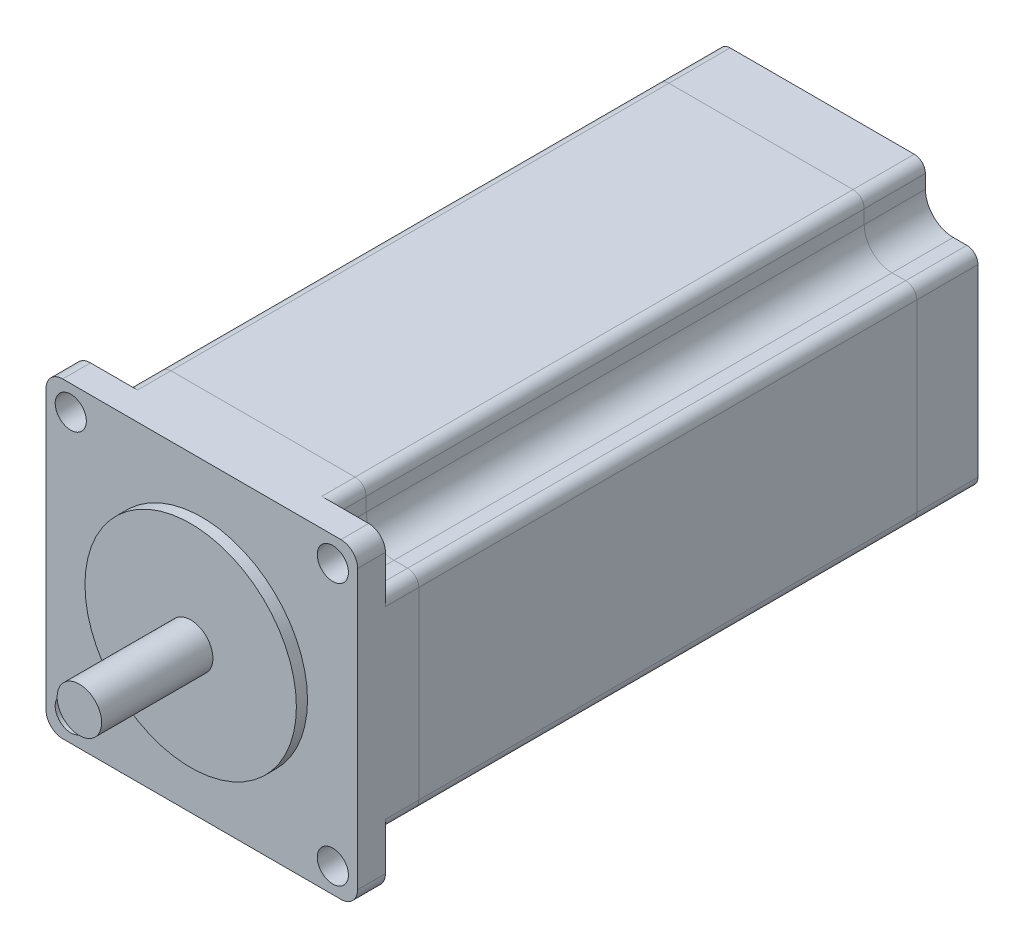
SolidWorks part; units mm, degrees
ref_plane "Front Plane" through (0, 0, 0) normal (0, 0, 1) x (1, 0, 0)
ref_plane "Top Plane" through (0, 0, 0) normal (0, 1, 0) x (1, 0, 0)
ref_plane "Right Plane" through (0, 0, 0) normal (1, 0, 0) x (0, 0, -1)
ref_plane "Plane1" through (0, 0, 0) normal (0, 0, -1) x (-1, 0, 0)
ref_axis "Axis Motor" through (0, 0, -24.3683) along (0, 0, 1)
sketch "Sketch1" plane through (0, 0, 0) normal (0, 0, -1) x (-1, 0, 0)
  line L0 (-23, 28) -> (-28, 23)
  line L1 (-28, 23) -> (-28, -23)
  line L2 (-28, -23) -> (-23, -28)
  line L3 (-23, -28) -> (23, -28)
  line L4 (23, -28) -> (28, -23)
  line L5 (28, -23) -> (28, 23)
  line L6 (28, 23) -> (23, 28)
  line L7 (23, 28) -> (-23, 28)
  line L8 (0, 0) -> (28, 0) construction
  line L9 (0, 0) -> (0, -13.2452) construction
  point P8 (0, -28)
  point P10 (28, 0)
  dimension "D1" = 56
  dimension "D2" = 56
  dimension "D3" = 135
  dimension "D4" = 5
extrude "Boss-Extrude1" add sketch "Sketch1" against normal blind 11.5
sketch "Sketch2" plane through (0, 0, 11.5) normal (0, 0, 1) x (1, 0, 0)
  line L12 (23, 28) -> (-23, 28)
  line L13 (-23, 28) -> (-28, 23)
  line L14 (-28, 23) -> (-28, -23)
  line L15 (-28, -23) -> (-23, -28)
  line L16 (-23, -28) -> (23, -28)
  line L17 (23, -28) -> (28, -23)
  line L18 (28, -23) -> (28, 23)
  line L19 (28, 23) -> (23, 28)
  line L20 (23, 28) -> (-23, 28)
  line L21 (-23, 28) -> (-28, 23)
  line L22 (-28, 23) -> (-28, -23)
  line L23 (-28, -23) -> (-23, -28)
  line L24 (-23, -28) -> (23, -28)
  line L25 (23, -28) -> (28, -23)
  line L26 (28, -23) -> (28, 23)
  line L27 (28, 23) -> (23, 28)
  dimension "D1" = 0
extrude "Boss-Extrude2" add sketch "Sketch2" along normal blind 90
sketch "Sketch3" plane through (0, 0, 101.5) normal (0, 0, 1) x (1, 0, 0)
  line L15 (28, 23) -> (23, 28)
  line L16 (23, 28) -> (-23, 28)
  line L17 (-23, 28) -> (-28, 23)
  line L18 (-28, 23) -> (-28, -23)
  line L19 (-28, -23) -> (-23, -28)
  line L20 (-23, -28) -> (23, -28)
  line L21 (23, -28) -> (28, -23)
  line L22 (28, -23) -> (28, 23)
  line L24 (28, 28) -> (-28, 28)
  line L26 (-28, 28) -> (-28, -28)
  line L28 (-28, -28) -> (28, -28)
  line L30 (28, -28) -> (28, 28)
  dimension "D1" = 0
extrude "Boss-Extrude3" add sketch "Sketch3" along normal blind 10
ref_plane "Plane2" through (0, 0, 3.65) normal (0, 0, 1) x (1, 0, 0)
sketch "Sketch4" plane through (0, 0, 3.65) normal (0, 0, 1) x (1, 0, 0)
  line L0 (-31, 1.25) -> (-31, 0.65)
  line L1 (-31, 0.65) -> (-21, 0.65)
  line L2 (-21, 0.65) -> (-21, 1.25)
  line L3 (-21, 1.25) -> (-31, 1.25)
  line L4 (-31, 0.65) -> (-21, 0.65) construction
revolve "Revolve1" add sketch "Sketch4" angle 360 about L4 reverse direction yes
sketch "Sketch5" plane through (0, 0, 3.65) normal (0, 0, 1) x (1, 0, 0)
  line L0 (-31, -0.05) -> (-31, -0.65)
  line L1 (-31, -0.65) -> (-21, -0.65)
  line L2 (-21, -0.65) -> (-21, -0.05)
  line L3 (-21, -0.05) -> (-31, -0.05)
  line L4 (-31, -0.65) -> (-21, -0.65) construction
revolve "Revolve2" add sketch "Sketch5" angle 360 about L4 reverse direction yes
ref_plane "Plane3" through (0, 0, 4.95) normal (0, 0, 1) x (1, 0, 0)
sketch "Sketch6" plane through (0, 0, 4.95) normal (0, 0, 1) x (1, 0, 0)
  line L0 (-31, -0.05) -> (-31, -0.65)
  line L1 (-31, -0.65) -> (-21, -0.65)
  line L2 (-21, -0.65) -> (-21, -0.05)
  line L3 (-21, -0.05) -> (-31, -0.05)
  line L4 (-31, -0.65) -> (-21, -0.65) construction
revolve "Revolve3" add sketch "Sketch6" angle 360 about L4 reverse direction yes
sketch "Sketch7" plane through (0, 0, 4.95) normal (0, 0, 1) x (1, 0, 0)
  line L0 (-31, 1.25) -> (-31, 0.65)
  line L1 (-31, 0.65) -> (-21, 0.65)
  line L2 (-21, 0.65) -> (-21, 1.25)
  line L3 (-21, 1.25) -> (-31, 1.25)
  line L4 (-31, 0.65) -> (-21, 0.65) construction
revolve "Revolve4" add sketch "Sketch7" angle 360 about L4 reverse direction yes
ref_plane "Plane4" through (0, 0, 0) normal (0, -1, 0) x (1, 0, 0)
sketch "Sketch8" plane through (0, 0, 0) normal (0, -1, 0) x (1, 0, 0)
  line L0 (4, 133.5) -> (0, 133.5)
  line L1 (0, 133.5) -> (0, 111.5)
  line L2 (0, 111.5) -> (19, 111.5)
  line L3 (19, 111.5) -> (19, 113.5)
  line L4 (19, 113.5) -> (4, 113.5)
  line L5 (4, 113.5) -> (4, 133.5)
  line L6 (0, 133.5) -> (0, 111.5) construction
  line L7 (28, 111.5) -> (-28, 111.5) construction
  line L8 (0, -24.3683) -> (0, 71.8516) construction
  dimension "D1" = 2
  dimension "D2" = 20
  dimension "D3" = 4
  dimension "D4" = 19
revolve "Revolve5" add sketch "Sketch8" angle 360 about L6 reverse direction yes
hole_wizard "Hole1" positions "Sketch10" profile "Sketch9" legacy
sketch "Sketch10" plane through (0, 0, 111.5) normal (0, 0, 1) x (1, 0, 0)
  line L1 (-23.55, 23.55) -> (0, 0) construction
  line L2 (0, 0) -> (0, 42.4264) construction
  circle A0 centre (0, 0) radius 33.3047 construction
  circle A1 centre (-23.55, 23.55) radius 2.8
  point P0 (-23.55, 23.55)
  dimension "D1" = 41.5
  dimension "D3" = 5.6
  dimension "D2" = 45
sketch "Sketch9" plane through (-23.55, 23.55, 111.5) normal (1, 0, 0) x (0, -1, 0)
  line L0 (0, 0) -> (0, 5)
  line L1 (0, 5) -> (2.8, 5)
  line L2 (2.8, 5) -> (2.8, 0)
  line L3 (2.8, 0) -> (0, 0)
  line L4 (0, 110) -> (0, -10) construction
  dimension "Diameter" = 5.6
  dimension "Depth" = 5
hole_wizard "Hole2" positions "Sketch12" profile "Sketch11" legacy
sketch "Sketch12" plane through (0, 0, 111.5) normal (0, 0, 1) x (1, 0, 0)
  line L0 (0, 0) -> (-36.6834, 0) construction
  point P0 (-23.55, -23.55)
  point P5 (-23.55, 23.55)
sketch "Sketch11" plane through (-23.55, -23.55, 111.5) normal (1, 0, 0) x (0, -1, 0)
  line L0 (0, 0) -> (0, 5)
  line L1 (0, 5) -> (2.8, 5)
  line L2 (2.8, 5) -> (2.8, 0)
  line L3 (2.8, 0) -> (0, 0)
  line L4 (0, 110) -> (0, -10) construction
  dimension "Diameter" = 5.6
  dimension "Depth" = 5
mirror "Mirror2" about plane through (0, 0, 0) normal (1, 0, 0) of "Hole1", "Hole2"
sketch "Sketch34" plane through (0, 0, 101.5) normal (0, 0, -1) x (-1, 0, 0)
  line L0 (0, 0) -> (0, 60.2383) construction
  line L1 (0, 0) -> (33.4585, 0) construction
  line L2 (18.55, 23.55) -> (18.55, 34.6712)
  line L3 (18.55, 34.6712) -> (31.9747, 34.6712)
  line L4 (31.9747, 34.6712) -> (31.9747, 18.55)
  line L5 (23.55, 18.55) -> (31.9747, 18.55)
  line L6 (23.55, -18.55) -> (31.9747, -18.55)
  line L7 (31.9747, -34.6712) -> (31.9747, -18.55)
  line L8 (18.55, -34.6712) -> (31.9747, -34.6712)
  line L9 (18.55, -23.55) -> (18.55, -34.6712)
  line L10 (-18.55, -23.55) -> (-18.55, -34.6712)
  line L11 (-18.55, -34.6712) -> (-31.9747, -34.6712)
  line L12 (-31.9747, -34.6712) -> (-31.9747, -18.55)
  line L13 (-23.55, -18.55) -> (-31.9747, -18.55)
  line L14 (-23.55, 18.55) -> (-31.9747, 18.55)
  line L15 (-31.9747, 34.6712) -> (-31.9747, 18.55)
  line L16 (-18.55, 34.6712) -> (-31.9747, 34.6712)
  line L17 (-18.55, 23.55) -> (-18.55, 34.6712)
  arc A0 (18.55, 23.55) -> (23.55, 18.55) centre (23.55, 23.55) ccw
  circle A1 centre (23.55, 23.55) radius 2.8 construction
  arc A5 (18.55, -23.55) -> (23.55, -18.55) centre (23.55, -23.55) cw
  arc A6 (-18.55, -23.55) -> (-23.55, -18.55) centre (-23.55, -23.55) ccw
  arc A7 (-18.55, 23.55) -> (-23.55, 18.55) centre (-23.55, 23.55) cw
  dimension "D1" = 10
extrude "Cut-Extrude9" cut sketch "Sketch34" along normal through all and the other way offset from surface 5 other way up to face at (26.35, -23.55, 111.5)
fillet "Fillet3" radius 2 8 edges at (18.55, -28, 53.25) (28, -18.55, 53.25) (-18.55, -28, 53.25) (-28, -18.55, 53.25) (-28, 18.55, 53.25) (-18.55, 28, 53.25) (28, 18.55, 53.25) (18.55, 28, 53.25)
fillet "Fillet4" radius 3 4 edges at (28, 28, 109) (-28, 28, 109) (28, -28, 109) (-28, -28, 109)
sketch "Sketch17" plane through (0, 0, 0) normal (0, 0, -1) x (-1, 0, 0)
  circle A0 centre (0, 0) radius 4 construction
  circle A1 centre (0, 0) radius 4
extrude "Boss-Extrude4" add sketch "Sketch17" along normal blind 12
sketch "Sketch31" plane through (28, 0, 0) normal (1, 0, 0) x (0, 0, -1)
  line L0 (0, 16.55) -> (0, -16.55) construction
  line L1 (-11, 32.881) -> (-100.5, 32.881)
  line L2 (-11, 32.881) -> (-11, -32.0284)
  line L3 (-11, -32.0284) -> (-100.5, -32.0284)
  line L4 (-100.5, 32.881) -> (-100.5, -32.0284)
  line L7 (-111.5, -25) -> (-111.5, 25) construction
  dimension "D1" = 11
  dimension "D2" = 11
split line "Split Line2"
